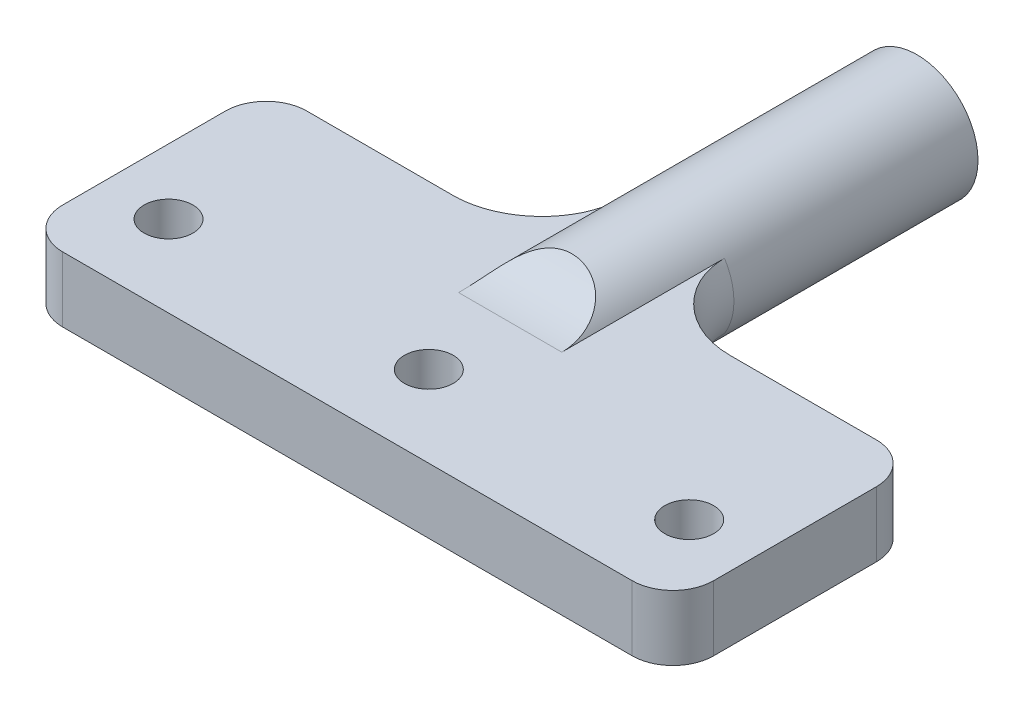
SolidWorks part; units mm, degrees
ref_plane "Front Plane" through (0, 0, 0) normal (0, 0, 1) x (1, 0, 0)
ref_plane "Top Plane" through (0, 0, 0) normal (0, 1, 0) x (1, 0, 0)
ref_plane "Right Plane" through (0, 0, 0) normal (1, 0, 0) x (0, 0, -1)
sketch "Sketch1" plane through (0, 0, 0) normal (0, 0, 1) x (1, 0, 0)
  circle A0 centre (0, 0) radius 7.5
  dimension "D1" = 15
extrude "Boss-Extrude1" add sketch "Sketch1" along normal blind 40
sketch "Sketch2" plane through (0, 0, 40) normal (0, 0, 1) x (1, 0, 0)
  line L1 (-40, 4) -> (40, 4)
  line L2 (-40, 4) -> (-40, -4)
  line L3 (-40, -4) -> (40, -4)
  line L4 (40, 4) -> (40, -4)
  line L5 (-40, 4) -> (40, -4) construction
  line L6 (-40, -4) -> (40, 4) construction
  point P0 (0, 0)
  dimension "D1" = 80
  dimension "D2" = 8
extrude "Boss-Extrude2" add sketch "Sketch2" along normal blind 30
fillet "Fillet1" radius 10 2 edges at (7.5, 0, 40) (-7.5, 0, 40)
fillet "Fillet2" radius 10 2 edges at (0, -4, 40) (0, 4, 40)
fillet "Fillet3" radius 5 4 edges at (-40, 0, 70) (40, 0, 70) (-40, 0, 40) (40, 0, 40)
sketch "Sketch3" plane through (0, 4, 0) normal (0, 1, 0) x (1, 0, 0)
  line L0 (-40, -60) -> (40, -60) construction
  line L1 (-40, -65) -> (-40, -45) construction
  line L2 (40, -65) -> (40, -45) construction
  line L3 (35, -70) -> (-35, -70) construction
  circle A0 centre (-32, -60) radius 3
  circle A1 centre (32, -60) radius 3
  circle A2 centre (0, -60) radius 3
  dimension "D2" = 6
  dimension "D3" = 6
  dimension "D6" = 6
  dimension "D1" = 10
  dimension "D4" = 8
  dimension "D5" = 8
extrude "Cut-Extrude1" cut sketch "Sketch3" against normal blind 19
